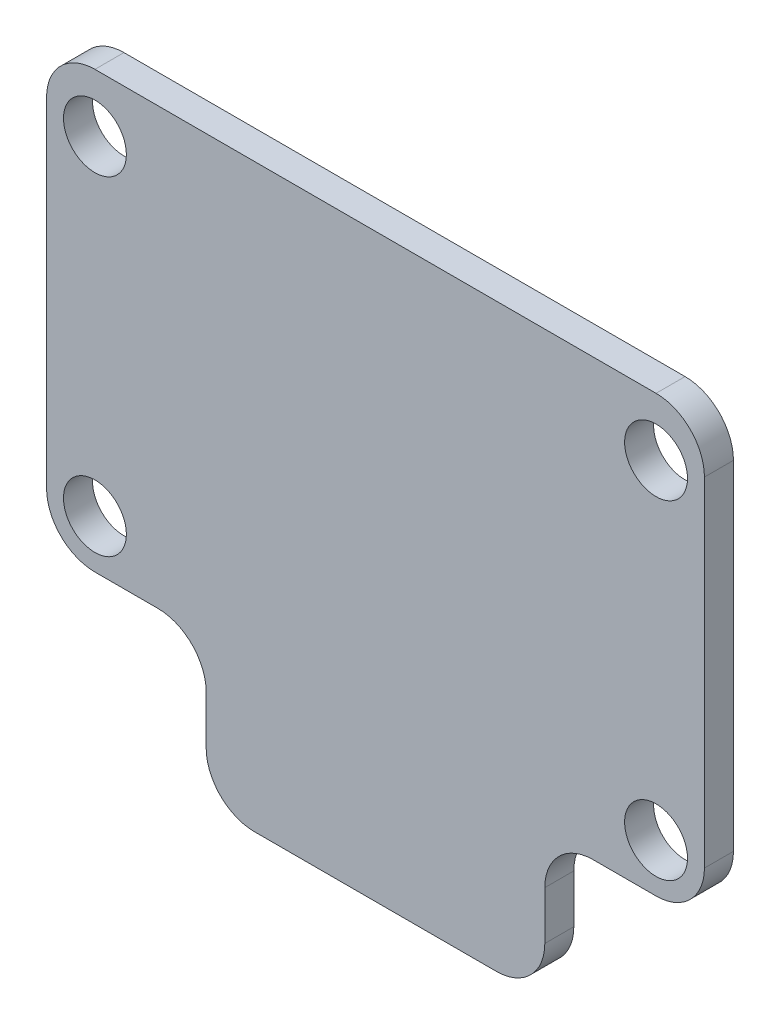
SolidWorks part; units mm, degrees
ref_plane "Plan de face" through (0, 0, 0) normal (0, 0, 1) x (1, 0, 0)
ref_plane "Plan de dessus" through (0, 0, 0) normal (0, 1, 0) x (1, 0, 0)
ref_plane "Plan de droite" through (0, 0, 0) normal (1, 0, 0) x (0, 0, -1)
sketch "Esquisse2" plane through (0, 0, 0) normal (0, 0, 1) x (1, 0, 0)
  line L0 (39.2085, -84.0985) -> (39.2085, -5.0985) construction
  line L1 (107.2085, 1.9015) -> (39.2085, 1.9015)
  line L2 (107.2085, 1.9015) -> (107.2085, -43.0985)
  line L3 (107.2085, -43.0985) -> (90.7085, -43.0985)
  line L4 (39.2085, 1.9015) -> (39.2085, -43.0985)
  line L5 (55.7085, -43.0985) -> (39.2085, -43.0985)
  line L7 (90.7085, -43.0985) -> (90.7085, -58.0985)
  line L8 (90.7085, -58.0985) -> (55.7085, -58.0985)
  line L9 (55.7085, -43.0985) -> (55.7085, -58.0985)
  circle A0 centre (102.2085, -4.0985) radius 3.25
  circle A1 centre (102.2085, -38.0985) radius 3.25
  circle A2 centre (44.2085, -38.0985) radius 3.25
  circle A3 centre (44.2085, -4.0985) radius 3.25
  point P23 (73.2085, -58.0985)
  point P24 (73.2085, 1.9015)
  dimension "D4" = 6.5
  dimension "D1" = 45
  dimension "D2" = 15
  dimension "D3" = 35
extrude "Boss.-Extru.1" add sketch "Esquisse2" along normal blind 3
fillet "Congé1" radius 5 8 edges at (39.2085, 1.9015, 1.5) (39.2085, -43.0985, 1.5) (55.7085, -58.0985, 1.5) (55.7085, -43.0985, 1.5) (90.7085, -58.0985, 1.5) (90.7085, -43.0985, 1.5) (107.2085, -43.0985, 1.5) (107.2085, 1.9015, 1.5)
